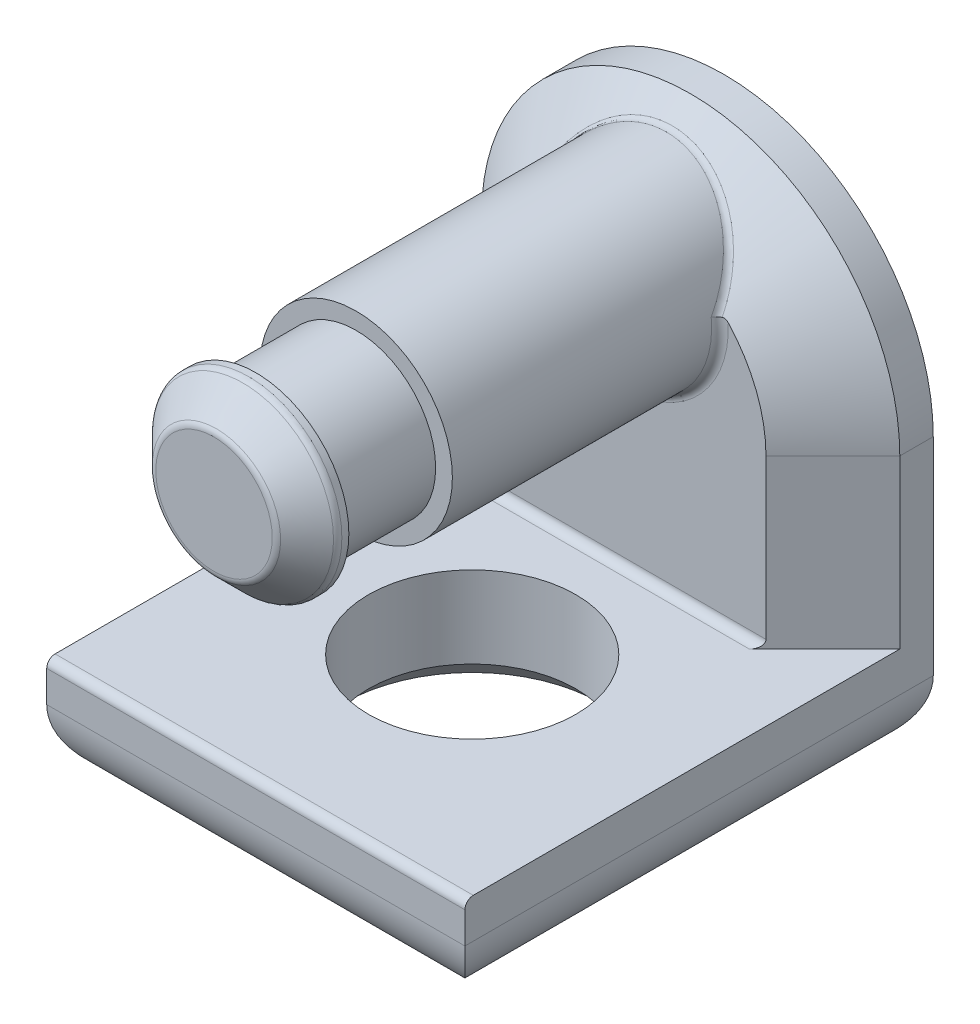
SolidWorks part; units mm, degrees
ref_plane "Front Plane" through (0, 0, 0) normal (0, 0, 1) x (1, 0, 0)
ref_plane "Top Plane" through (0, 0, 0) normal (0, 1, 0) x (1, 0, 0)
ref_plane "Right Plane" through (0, 0, 0) normal (1, 0, 0) x (0, 0, -1)
sketch "Sketch1" plane through (0, 0, 0) normal (0, 0, 1) x (1, 0, 0)
  line L0 (5, 0) -> (5, 5) construction
  line L5 (0, 0) -> (10, 0)
  line L6 (0, 0) -> (0, 3.9991)
  line L8 (10, 0) -> (10, 3.9991)
  arc A1 (0, 3.9991) -> (10, 3.9991) centre (5, 3.9991) cw
  point P0 (0, 0)
  dimension "D1" = 10
  dimension "D2" = 5
extrude "Boss-Extrude1" add sketch "Sketch1" along normal blind 2.4
ref_plane "Plane1" through (0, 0, 2.4) normal (0, 0, 1) x (1, 0, 0)
sketch "Sketch2" plane through (0, 0, 2.4) normal (0, 0, 1) x (1, 0, 0)
  line L0 (5, 0) -> (5, 6.2) construction
  line L1 (0, 0) -> (10, 0) construction
  circle A0 centre (5, 6.2) radius 2.3
  dimension "D1" = 6.2
  dimension "D2" = 4.6
extrude "Boss-Extrude2" add sketch "Sketch2" along normal blind 6.4
ref_plane "Plane2" through (0, 0, 8.8) normal (0, 0, 1) x (1, 0, 0)
sketch "Sketch3" plane through (0, 0, 8.8) normal (0, 0, 1) x (1, 0, 0)
  circle A0 centre (5, 6.2) radius 1.9
  circle A1 centre (5, 6.2) radius 2.3 construction
  dimension "D1" = 3.8
extrude "Boss-Extrude3" add sketch "Sketch3" along normal blind 2.4
ref_plane "Plane3" through (0, 0, 11.2) normal (0, 0, 1) x (1, 0, 0)
sketch "Sketch4" plane through (0, 0, 11.2) normal (0, 0, 1) x (1, 0, 0)
  circle A0 centre (5, 6.2) radius 2.225
  dimension "D1" = 4.45
extrude "Boss-Extrude4" add sketch "Sketch4" along normal blind 1
chamfer "Chamfer1" distance 0.75 angle 45 1 edges at (7.225, 6.2, 12.2)
fillet "Fillet1" radius 0.2 2 edges at (7.225, 6.2, 11.45) (6.475, 6.2, 12.2)
chamfer "Chamfer3" distance 1.6 angle 45 3 edges at (10, 1.9995, 2.4) (0, 1.9995, 2.4) (5, 8.9991, 2.4)
sketch "Sketch5" plane through (0, 0, 0) normal (0, 0, 1) x (1, 0, 0)
  line L1 (0, 0) -> (10, 0)
  line L2 (0, 0) -> (0, -2.55)
  line L3 (0, -2.55) -> (10, -2.55)
  line L4 (10, 0) -> (10, -2.55)
  dimension "D1" = 2.55
  dimension "D2" = 10
extrude "Boss-Extrude5" add sketch "Sketch5" along normal blind 11.2
ref_plane "Plane4" through (0, -2.55, 0) normal (0, -1, 0) x (-1, 0, 0)
sketch "Sketch6" plane through (0, -2.55, 0) normal (0, -1, 0) x (-1, 0, 0)
  line L0 (-10, 0) -> (0, -11.2) construction
  line L1 (0, 0) -> (-10, -11.2) construction
  line L2 (-6.5418, -11.2) -> (6.5418, -11.2) construction
  line L3 (0, -11.2) -> (-10, -11.2) construction
  line L4 (-5, -5.6) -> (-5, -11.2) construction
  line L5 (-2.775, -11.2) -> (-7.225, -11.2) construction
  line L6 (-5, -11.2) -> (-5, -6.0257) construction
  circle A0 centre (-5, -6.0257) radius 2.48
extrude "Cut-Extrude1" cut sketch "Sketch6" against normal blind 2.7
chamfer "Chamfer2" distance 0.6 angle 45 1 edges at (5, -2.55, 3.5457)
fillet "Fillet2" radius 1.6 4 edges at (0, -2.55, 5.6) (5, -2.55, 11.2) (10, -2.55, 5.6) (5, -2.55, 0)
fillet "Fillet3" radius 0.2 3 edges at (5, 0, 11.2) (5, 0, 2.4) (5, 3.9, 2.4)
fillet "Fillet4" radius 0.2 1 edges at (4.9397, 8.4992, 1.2994)
